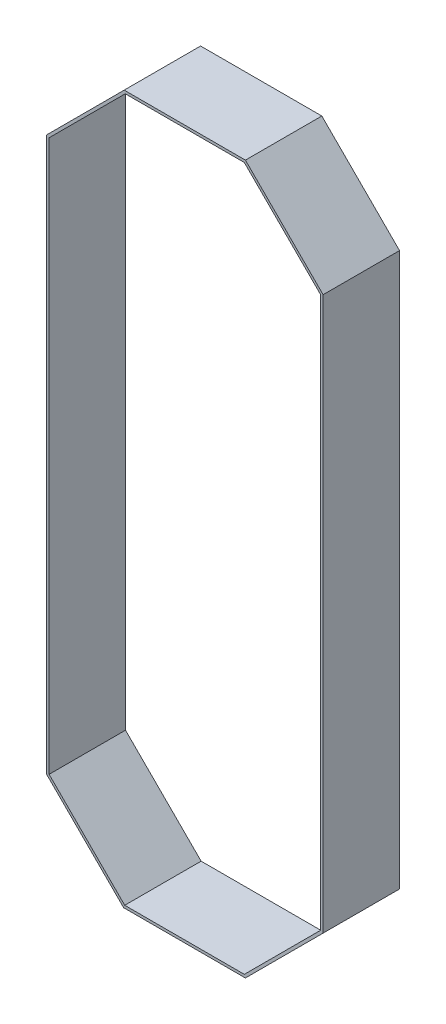
SolidWorks part; units mm, degrees
ref_plane "Спереди" through (0, 0, 0) normal (0, 0, 1) x (1, 0, 0)
ref_plane "Сверху" through (0, 0, 0) normal (0, 1, 0) x (1, 0, 0)
ref_plane "Справа" through (0, 0, 0) normal (1, 0, 0) x (0, 0, -1)
sketch "Эскиз1" plane through (0, 0, 0) normal (0, 0, 1) x (1, 0, 0)
  line L0 (105.1646, 581.9216) -> (46.1815, 640.9047)
  line L1 (46.1815, 640.9047) -> (-45.8522, 640.9047)
  line L2 (-45.8522, 640.9047) -> (-104.8354, 581.9216)
  line L3 (-104.8354, 581.9216) -> (-104.8354, 161.779)
  line L4 (-104.8354, 161.779) -> (-46.2674, 103.211)
  line L5 (-46.2674, 103.211) -> (46.1729, 103.211)
  line L6 (46.1729, 103.211) -> (105.1646, 162.2028)
  line L7 (105.1646, 162.2028) -> (105.1646, 581.9216)
  line L8 (0.1646, 640.9047) -> (0.1646, 713.1182) construction
  dimension "D1" = 105
  dimension "D2" = 105
extrude "Вытянуть-Тонкостенный1" add sketch "Эскиз1" along normal up to surface (58 mm away) thin thin type one direction reverse wall 2
